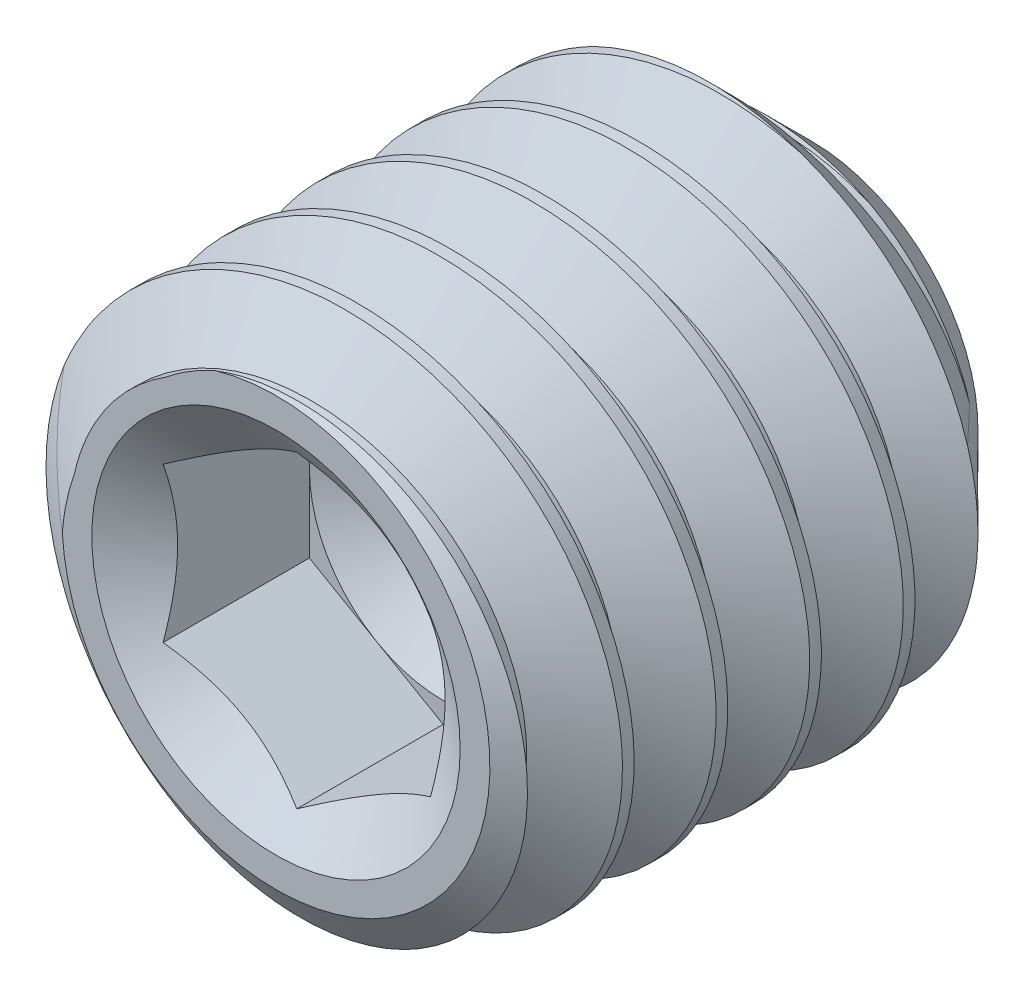
SolidWorks part; units mm, degrees
material "SUS304(低発塵)"
ref_plane "Front Plane" through (0, 0, 0) normal (0, 0, 1) x (1, 0, 0)
ref_plane "Top Plane" through (0, 0, 0) normal (0, 1, 0) x (1, 0, 0)
ref_plane "Right Plane" through (0, 0, 0) normal (1, 0, 0) x (0, 0, -1)
sketch "Sketch1" plane through (0, 0, 0) normal (1, 0, 0) x (0, 0, -1)
  line L0 (-1.7078, 0) -> (-1.7078, 1.6)
  line L1 (-1.7078, 1.6) -> (-1.4277, 2)
  line L2 (-1.4277, 2) -> (1.5422, 2)
  line L3 (1.5422, 2) -> (2.2922, 1.25)
  line L5 (1.7078, 0) -> (-1.7078, 0)
  line L6 (1.7078, 0) -> (2.2922, 0) construction
  line L7 (2.2922, 0) -> (2.2922, 1.25) construction
  line L8 (2.2922, -1.25) -> (1.7078, 0) construction
  line L9 (-1.4277, -2) -> (1.5422, -2) construction
  line L10 (0, 0) -> (0, -0.7) construction
  line L11 (1.7078, 0) -> (2.1494, 0.735)
  line L12 (1.7078, 0) -> (2.1494, -0.735) construction
  arc A0 (2.1494, 0.735) -> (2.2922, 1.25) centre (1.2922, 1.25) ccw
  arc A1 (2.1494, -0.735) -> (2.2922, -1.25) centre (1.2922, -1.25) cw construction
  point P11 (-1.7078, 2)
  point P12 (-0.1578, -2)
  point P13 (0.0422, -2)
  point P14 (2.2922, 2)
  dimension "D5" = 1
  dimension "Thread Size" = 4
  dimension "Length" = 4
  dimension "D3" = 35
  dimension "D6" = 45
  dimension "D7" = 3.2
  dimension "Thread Pitch" = 0.7
  dimension "D2" = 1.75
  dimension "D4" = 59
  dimension "D8" = 2.5
  dimension "D1" = 2.45
sketch "Sketch2" plane through (0, 0, 0) normal (0, 0, 1) x (1, 0, 0)
  line L1 (1, 0.5774) -> (0, 1.1547) construction
  line L2 (0, 1.1547) -> (-1, 0.5774) construction
  line L3 (-1, 0.5774) -> (-1, -0.5774) construction
  line L4 (-1, -0.5774) -> (0, -1.1547) construction
  line L5 (0, -1.1547) -> (1, -0.5774) construction
  line L6 (1, -0.5774) -> (1, 0.5774) construction
  circle A0 centre (0, 0) radius 1 construction
  circle A1 centre (0, 0) radius 2 construction
  dimension "Drive Size" = 2
sketch "Sketch4" plane through (0, 0, 0) normal (1, 0, 0) x (0, 0, -1)
  line L0 (1.7078, 0) -> (2.1494, 0.735) construction
  line L1 (-1.4277, 2) -> (1.5422, 2) construction
  line L2 (-1.7078, 0) -> (-1.7078, 1.6) construction
  line L3 (1.7078, 0) -> (-1.7078, 0) construction
  line L4 (1.7078, 0) -> (2.1494, 0.735)
  line L5 (1.5422, 2) -> (2.2922, 1.25) construction
  line L6 (1.5422, 2) -> (2.2922, 1.25)
  line L8 (1.7078, 0) -> (-1.7078, 0)
  line L9 (-1.7078, 0) -> (-1.7078, 1.6)
  line L10 (-1.4277, 2) -> (1.5422, 2)
  line L11 (-1.7078, 1.6) -> (-1.4277, 2) construction
  line L12 (-1.7078, 1.6) -> (-1.4277, 2)
  arc A0 (2.1494, 0.735) -> (2.2922, 1.25) centre (1.2922, 1.25) ccw construction
  arc A1 (2.1494, 0.735) -> (2.2922, 1.25) centre (1.2922, 1.25) ccw
revolve "Revolve1" add sketch "Sketch4" angle 360 about L8
sketch "Sketch6" plane through (0, 0, 1.7078) normal (0, 0, 1) x (1, 0, 0)
  line L1 (1, 0.5774) -> (0, 1.1547)
  line L2 (0, 1.1547) -> (-1, 0.5774)
  line L3 (-1, 0.5774) -> (-1, -0.5774)
  line L4 (-1, -0.5774) -> (0, -1.1547)
  line L5 (0, -1.1547) -> (1, -0.5774)
  line L6 (1, -0.5774) -> (1, 0.5774)
  circle A0 centre (0, 0) radius 1 construction
  dimension "D1" = 2
extrude "Cut-Extrude3" cut sketch "Sketch6" against normal blind 1.25
sketch "Sketch7" plane through (0, 0, 1.7078) normal (0, 0, 1) x (1, 0, 0)
  line L0 (0, 1.1547) -> (0, 1.6) construction
  circle A0 centre (0, 0) radius 1.3774
  circle A2 centre (0, 0) radius 1.6 construction
  point P6 (0, 1.3774)
  point P10 (0, 1.3774)
extrude "Cut-Extrude4" cut sketch "Sketch7" against normal through all draft 55
sketch "Sketch8" plane through (0, 0, 0.4578) normal (0, 0, 1) x (1, 0, 0)
  circle A0 centre (0, 0) radius 1 construction
  circle A1 centre (0, 0) radius 1
extrude "Cut-Extrude5" cut sketch "Sketch8" against normal through all draft 60
ref_plane "Plane1" through (0, 0, -2.2922) normal (0, 0, 1) x (1, 0, 0)
sketch "Sketch9" plane through (0, 0, -2.2922) normal (0, 0, 1) x (1, 0, 0)
  circle A0 centre (0, 0) radius 2 construction
  circle A1 centre (0, 0) radius 2
curve "Helix/Spiral1" pitch 0.7 height 4.7 radius 2 centre (0, 0, -2.2922) axis (0, 0, 1) start towards (0, 1, 0)
sketch "Sketch10" plane through (0, 0, 0) normal (1, 0, 0) x (0, 0, -1)
  line L0 (2.2922, 2) -> (2.9047, 2)
  line L1 (2.9047, 2) -> (2.6422, 1.5453)
  line L2 (2.5547, 1.5453) -> (2.2922, 2)
  line L3 (2.5547, 1.5453) -> (2.6422, 1.5453)
  line L4 (2.5985, 1.5453) -> (2.5985, 2) construction
  line L5 (2.4235, 1.7727) -> (2.7735, 1.7727) construction
  point P10 (2.5985, 1.7727)
  dimension "D1" = 60
  dimension "D2" = 0.0875
  dimension "D3" = 0.35
sweep "Cut-Sweep1" cut profiles "Sketch10" path "Helix/Spiral1"
equation "\"D7@Sketch1\" = \"Thread Size@Sketch1\" * .8"
equation "\"D3\"= \"Length@Sketch1\" + \"Thread Pitch@Sketch1\""
equation "\"D4\"= \"Thread Pitch@Sketch1\""
equation "\"D1@Sketch6\"=\"Drive Size@Sketch2\""
equation "\"D1@Cut-Extrude3\"=\"Drive Size@Sketch2\"*.625"
equation "\"D3@Helix/Spiral1\"=\"Length@Sketch1\"+\"Thread Pitch@Sketch1\""
equation "\"D4@Helix/Spiral1\"=\"Thread Pitch@Sketch1\""
equation "\"D2@Sketch10\"=\"Thread Pitch@Sketch1\"/8"
equation "\"D3@Sketch10\"=\"Thread Pitch@Sketch1\"/2"
equation "\"D2@Sketch1\"=\"Thread Pitch@Sketch1\"*2.5"
equation "\"D5@Sketch1\"=\"Thread Size@Sketch1\"*.25"
equation "\"D8@Sketch1\"=\"Thread Size@Sketch1\"*.625"
equation "\"D1@Sketch1\"=\"Thread Pitch@Sketch1\"*3.5"
